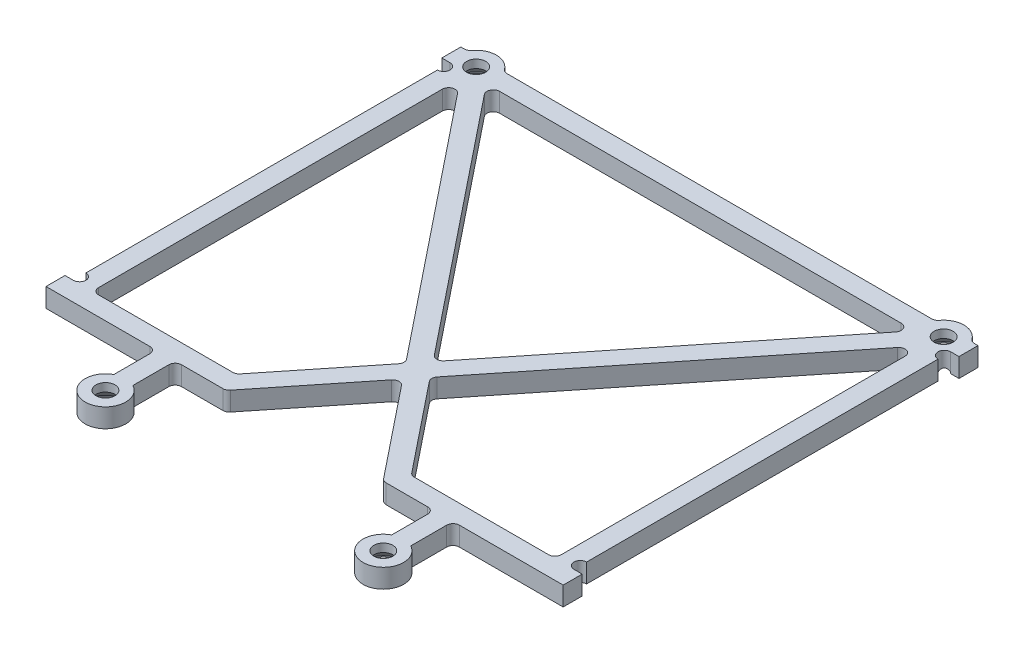
SolidWorks part; units mm, degrees
ref_plane "Front Plane" through (0, 0, 0) normal (0, 0, 1) x (1, 0, 0)
ref_plane "Top Plane" through (0, 0, 0) normal (0, 1, 0) x (1, 0, 0)
ref_plane "Right Plane" through (0, 0, 0) normal (1, 0, 0) x (0, 0, -1)
sketch "Sketch1" plane through (0, 0, 0) normal (0, 1, 0) x (1, 0, 0)
  line L0 (-36.88, 36.725) -> (36.88, 36.725) construction
  line L1 (-39.5, -24.225) -> (-39.5, 35.225)
  line L2 (21.92, -36.725) -> (-21.92, -36.725) construction
  line L3 (-36.5, -24.225) -> (-36.5, 35.225)
  line L4 (0, -40.095) -> (0, -36.725) construction
  line L5 (0, 36.725) -> (0, -36.725) construction
  line L6 (40.8, 38.225) -> (-40.8, 38.225)
  line L9 (40.8, 38.225) -> (40.8, 35.225)
  line L17 (40.8, 35.225) -> (-40.8, 35.225)
  line L18 (-40.8, 38.225) -> (-40.8, 35.225)
  line L23 (40.8, 38.225) -> (-40.8, 35.225) construction
  line L24 (40.8, 35.225) -> (-40.8, 38.225) construction
  line L60 (-21.92, -36.725) -> (36.88, 36.725) construction
  line L62 (21.92, -36.725) -> (-36.88, 36.725) construction
  line L66 (23.091, -35.7876) -> (-35.709, 37.6624)
  line L67 (20.749, -37.6624) -> (-38.051, 35.7876)
  line L68 (-20.749, -37.6624) -> (38.051, 35.7876)
  line L69 (-23.091, -35.7876) -> (35.709, 37.6624)
  line L71 (-36.5, 5.5) -> (-39.5, 5.5) construction
  line L73 (36.5, -24.225) -> (36.5, 35.225)
  line L74 (39.5, -24.225) -> (39.5, 35.225)
  line L75 (-36.5, -24.225) -> (-36.5, -27.225) construction
  line L76 (-40.8, -24.225) -> (40.8, -24.225)
  line L77 (-40.8, -24.225) -> (-40.8, -27.225)
  line L78 (-40.8, -27.225) -> (40.8, -27.225)
  line L79 (40.8, -24.225) -> (40.8, -27.225)
  line L80 (-40.8, -24.225) -> (40.8, -27.225) construction
  line L81 (-40.8, -27.225) -> (40.8, -24.225) construction
  line L82 (-21.92, -36.725) -> (-21.92, -27.225) construction
  line L84 (-23.42, -27.225) -> (-20.42, -27.225)
  line L85 (-23.42, -27.225) -> (-23.42, -33.8983)
  line L86 (-23.42, -33.8983) -> (-20.42, -33.8983)
  line L87 (-20.42, -27.225) -> (-20.42, -33.8983)
  line L88 (-23.42, -27.225) -> (-20.42, -33.8983) construction
  line L89 (-23.42, -33.8983) -> (-20.42, -27.225) construction
  line L90 (20.42, -27.225) -> (20.42, -33.8983)
  line L91 (23.42, -27.225) -> (23.42, -33.8983)
  circle A0 centre (21.92, -36.725) radius 1.5
  circle A1 centre (-21.92, -36.725) radius 1.5
  circle A2 centre (-36.88, 36.725) radius 1.5
  circle A3 centre (36.88, 36.725) radius 1.5
  circle A4 centre (-36.88, 36.725) radius 3.2
  circle A5 centre (-21.92, -36.725) radius 3.2
  circle A6 centre (21.92, -36.725) radius 3.2
  circle A7 centre (36.88, 36.725) radius 3.2
  circle A8 centre (0, -40.095) radius 16
  circle A9 centre (-39.5, 34.225) radius 1
  circle A10 centre (39.5, 34.225) radius 1
  circle A11 centre (-39.5, -23.225) radius 1
  circle A12 centre (39.5, -23.225) radius 1
  point P10 (0, 0)
  point P18 (-21.92, -30.5617)
  point P58 (0, -25.725)
  dimension "D4" = 3
  dimension "D5" = 6.4
  dimension "D6" = 32
  dimension "D9" = 3
  dimension "D17" = 2
  dimension "D1" = 74.958
  dimension "D2" = 43.84
  dimension "D3" = 73.76
  dimension "D7" = 3.37
  dimension "D8" = 81.6
  dimension "D10" = 79
  dimension "D13" = 1.5
  dimension "D14" = 1.5
  dimension "D15" = 1.5
  dimension "D16" = 1.5
  dimension "D18" = 11
extrude "Shape" add sketch "Sketch1" along normal blind 3 contours L9 | L9 | A4 L6 L18 L17 | L6 A4 | L6 A4 L17 L67 A2 | L66 A4 L6 A2 | L17 A4 L66 A2 | L67 A4 L17 L3 | L67 L3 L17 | A2 L67 L17 | A9 A4 L3 L67 L17 | A11 L76 L3 A4 A9 L1 | A4 L67 L69 L66 L17 | A4 L17 L66 | A7 L6 A4 L66 L17 L69 | L6 A7 L69 A3 | L6 A7 | L17 A7 L6 A3 L68 | A7 L17 L9 L6 | A7 A10 L17 L68 L73 | A3 L17 L68 | L69 A7 L17 A3 | L17 A7 L68 L73 | L73 L68 L17 | A7 L69 L17 | A7 L17 L69 L66 L68 | L76 A12 L74 A10 A7 L73 | L69 L67 L68 L66 | L69 L76 L68 L67 | L67 L76 L66 L68 | L77 L78 L69 L76 | A5 L69 L87 L78 L85 | A5 L87 L69 | L86 A5 L69 | L69 A5 L86 | L86 A5 L68 A1 L69 | L68 A5 L86 L69 A1 | L69 L78 L68 L76 | L67 L78 L66 L76 | L79 L76 L66 L78 | A6 L91 L78 L90 L66 | A6 L66 L90 | A6 L66 A0 L67 | L66 A6 L67 A0 region at (-27.9084, 0, 25.7017) region at (-37.9894, 0, -4.9296) region at (-37.7315, 0, -34.3772) region at (-13.114, 0, 25.725) region at (-6.4791, 0, 17.3668) region at (-21.9608, 0, 30.3398) region at (-36.8669, 0, -34.7667) region at (-35.5453, 0, -34.5717) region at (-17.9573, 0, -13.0823) region at (0, 0, 9.3436) region at (-39.0008, 0, -36.743) region at (-40.3721, 0, -36.725) region at (-22.2364, 0, 33.7343) region at (-22.4993, 0, 33.9863) region at (-35.0617, 0, -35.8515) region at (-37.5447, 0, -35.3415) region at (-33.9168, 0, -35.3014) region at (-20.7161, 0, 33.2949) region at (6.4791, 0, 17.3668) region at (17.9573, 0, -13.0823) region at (-36.88, 0, -38.9233) region at (-20.5884, 0, 35.1329) region at (-21.0809, 0, 33.7851) region at (0, 0, -36.7255) region at (-34.6096, 0, -37.2433) region at (13.114, 0, 25.725) region at (33.9168, 0, -35.3014) region at (27.9084, 0, 25.7017) region at (35.5453, 0, -34.5717) region at (35.0617, 0, -35.8515) region at (34.6096, 0, -37.2433) region at (36.88, 0, -38.9233) region at (20.6063, 0, 35.084) region at (19.7951, 0, 36.6157) region at (37.9894, 0, -4.9296) region at (36.8669, 0, -34.7667) region at (37.7315, 0, -34.3772) region at (39.0008, 0, -36.743) region at (40.3721, 0, -36.725) region at (20.7161, 0, 33.2949) region at (21.9608, 0, 30.3398) region at (37.5447, 0, -35.3415)
fillet "Mill fillets" radius 1 22 edges at (39.7067, 1.5, -38.225) (34.0533, 1.5, -38.225) (-39.7067, 1.5, -38.225) (-34.0533, 1.5, -38.225) (1.9214, 1.5, 9.3436) (-1.9214, 1.5, 9.3436) (33.7577, 1.5, -35.225) (-33.7577, 1.5, -35.225) (0, 1.5, 11.7438) (-36.5, 1.5, 24.225) (13.8346, 1.5, 24.225) (36.5, 1.5, 24.225) (-13.8346, 1.5, 24.225) (36.5, 1.5, -33.8501) (-36.5, 1.5, -33.8501) (0, 1.5, 6.9435) (-23.42, 1.5, 27.225) (20.42, 1.5, 27.225) (23.42, 1.5, 27.225) (-20.42, 1.5, 27.225) (12.3934, 1.5, 27.225) (-12.3934, 1.5, 27.225)
hole_wizard "M3 countersunks" positions "Sketch2" profile "Sketch3" countersink size "M3" standard "ANSI Metric" end condition through all
sketch "Sketch2" plane through (0, 0, 0) normal (0, -1, 0) x (-1, 0, 0)
  point P0 (21.92, -36.725)
  point P3 (-21.92, -36.725)
  point P6 (-36.88, 36.725)
  point P9 (36.88, 36.725)
sketch "Sketch3" plane through (-21.92, 0, 36.725) normal (1, 0, 0) x (0, 0, -1)
  line L0 (0, 0) -> (0, 3)
  line L1 (0, 3) -> (1.5, 3)
  line L2 (1.5, 3) -> (1.5, 1.7)
  line L3 (1.5, 1.7) -> (3, 0.2)
  line L4 (3, 0.2) -> (3, 0)
  line L6 (3, 0) -> (0, 0)
  line L7 (-1.5, 1.7) -> (-3, 0.2) construction
  line L11 (0, -6.35) -> (0, 107.95) construction
  dimension "Thru Hole Dia." = 3
  dimension "Thru Hole Depth" = 3
  dimension "C'Sink Dia." = 6
  dimension "C'Sink Angle" = 90
  dimension "Head Clearance" = 0.2
sketch "Coordinate system sketch" plane through (0, 0, 0) normal (0, -1, 0) x (1, 0, 0)
  line L0 (-36.88, -39.925) -> (-40.8, -39.925) construction
  line L1 (-40.8, -39.925) -> (-40.8, -38.225) construction
  arc A0 (-39.4514, -38.6298) -> (-34.3086, -38.6298) centre (-36.88, -36.725) ccw construction
  point P5 (0, 0)
